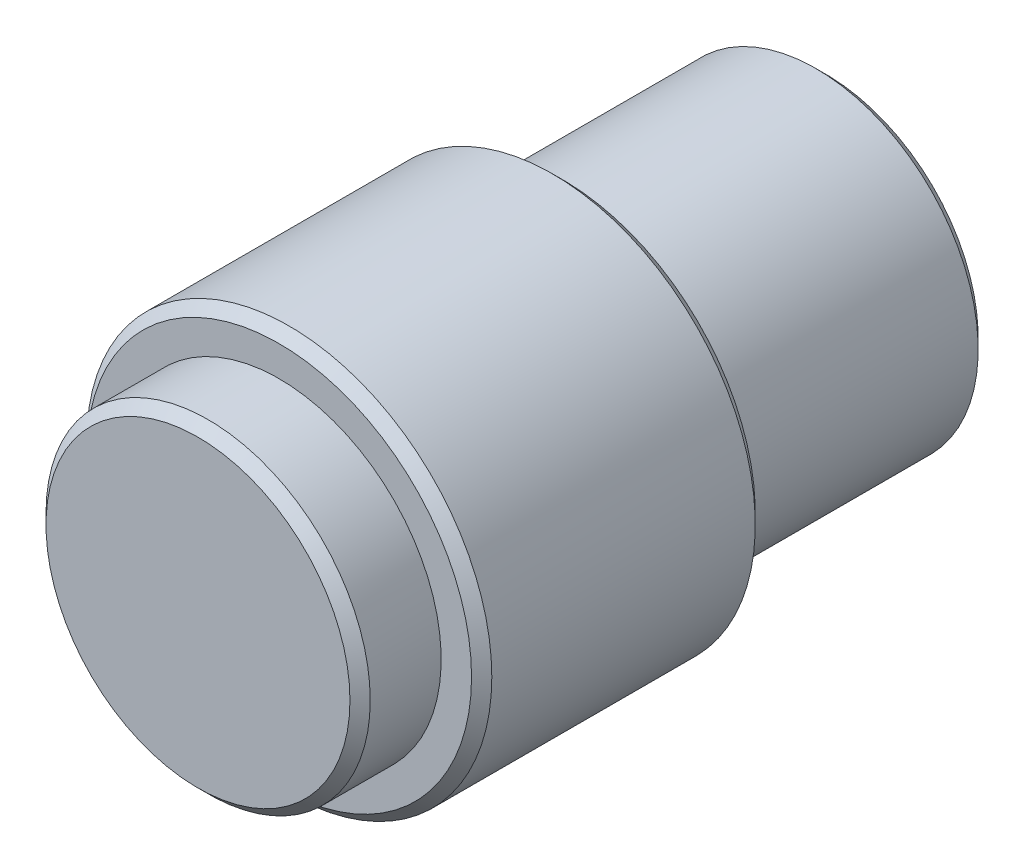
SolidWorks part; units mm, degrees
material "A2017"
ref_plane "正面" through (0, 0, 0) normal (0, 0, 1) x (1, 0, 0)
ref_plane "平面" through (0, 0, 0) normal (0, 1, 0) x (1, 0, 0)
ref_plane "右側面" through (0, 0, 0) normal (1, 0, 0) x (0, 0, -1)
sketch "ｽｹｯﾁ1" plane through (0, 0, 0) normal (1, 0, 0) x (0, 0, -1)
  line L0 (0, 0) -> (15.5, 0) construction
  line L1 (0, 0) -> (0, 4)
  line L2 (0, 4) -> (2, 4)
  line L3 (2, 4) -> (2, 5)
  line L4 (2, 5) -> (9, 5)
  line L5 (9, 5) -> (9, 4)
  line L6 (9, 4) -> (15.5, 4)
  line L7 (15.5, 4) -> (15.5, 0)
  line L8 (15.5, 0) -> (0, 0)
  dimension "D1" = 8
  dimension "D2" = 10
  dimension "D3" = 7
  dimension "D4" = 2
  dimension "D5" = 6.5
revolve "回転1" add sketch "ｽｹｯﾁ1" angle 360 about L8
chamfer "面取り1" distance 0.25 angle 45 4 edges at (-4, 0, -15.5) (-4, 0, 0) (-5, 0, -9) (-5, 0, -2)
